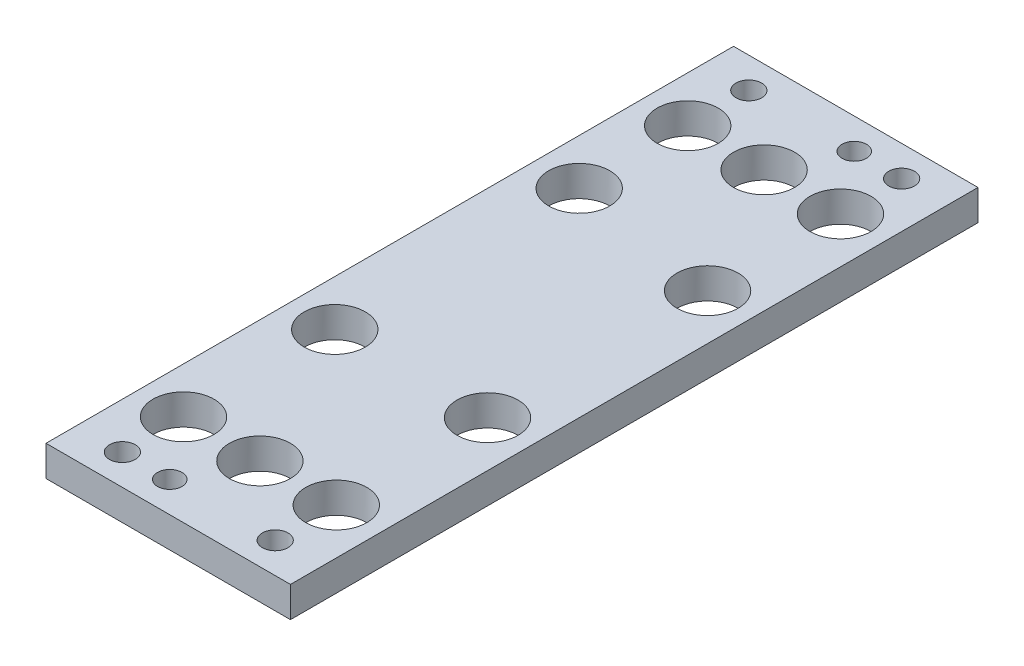
SolidWorks part; units mm, degrees
material "K110"
ref_plane "Front Plane" through (0, 0, 0) normal (0, 0, 1) x (1, 0, 0)
ref_plane "Top Plane" through (0, 0, 0) normal (0, 1, 0) x (1, 0, 0)
ref_plane "Right Plane" through (0, 0, 0) normal (1, 0, 0) x (0, 0, -1)
sketch "Sketch1" plane through (0, 0, 0) normal (0, 1, 0) x (1, 0, 0)
  line L1 (-40, -112.5) -> (40, -112.5)
  line L2 (-40, -112.5) -> (-40, 112.5)
  line L3 (-40, 112.5) -> (40, 112.5)
  line L4 (40, -112.5) -> (40, 112.5)
  line L5 (-40, -112.5) -> (40, 112.5) construction
  line L6 (-40, 112.5) -> (40, -112.5) construction
  point P0 (0, 0)
  dimension "D1" = 225
  dimension "D2" = 80
extrude "Boss-Extrude1" add sketch "Sketch1" against normal blind 10
sketch "Sketch2" plane through (0, 0, 0) normal (0, 1, 0) x (1, 0, 0)
  circle A0 centre (25, -82.5) radius 10 construction
  circle A1 centre (0, -82.5) radius 10 construction
  circle A2 centre (-25, -82.5) radius 10 construction
  circle A3 centre (25, -33) radius 10 construction
  circle A4 centre (-25, -33) radius 10 construction
  circle A6 centre (25, 39) radius 10 construction
  circle A7 centre (-25, 47) radius 10 construction
  circle A8 centre (-25, 82.5) radius 10 construction
  circle A9 centre (0, 82.5) radius 10 construction
  circle A10 centre (25, 82.5) radius 10 construction
  circle A11 centre (25, -82.5) radius 10
  circle A12 centre (0, -82.5) radius 10
  circle A13 centre (-25, -82.5) radius 10
  circle A14 centre (25, -33) radius 10
  circle A15 centre (-25, -33) radius 10
  circle A17 centre (25, 39) radius 10
  circle A18 centre (-25, 47) radius 10
  circle A19 centre (-25, 82.5) radius 10
  circle A20 centre (0, 82.5) radius 10
  circle A21 centre (25, 82.5) radius 10
extrude "Cut-Extrude1" cut sketch "Sketch2" against normal up to next
hole_wizard "M8 Clearance Hole1" positions "Sketch9" profile "Sketch8" hole size "M8" standard "ISO" end condition through all
sketch "Sketch9" plane through (0, 0, 0) normal (0, 1, 0) x (1, 0, 0)
  point P0 (25, -102.5)
  point P3 (-25, -102.5)
  point P6 (25, 102.5)
  point P9 (-25, 102.5)
sketch "Sketch8" plane through (25, 0, 102.5) normal (1, 0, 0) x (0, 0, 1)
  line L0 (0, 0) -> (0, 10)
  line L1 (0, 10) -> (4.2, 10)
  line L2 (4.2, 10) -> (4.2, 0)
  line L5 (4.2, 0) -> (0, 0)
  line L11 (0, -6.35) -> (0, 107.95) construction
  dimension "Thru Hole Dia." = 8.4
  dimension "Thru Hole Depth" = 10
hole_wizard "Ø8.0mm Dowel Hole1" positions "Sketch12" profile "Sketch11" hole size "Ø8.0" standard "ISO" end condition through all
sketch "Sketch12" plane through (0, 0, 0) normal (0, 1, 0) x (1, 0, 0)
  point P0 (-9.5, -102.5)
  point P3 (9.5, 102.5)
sketch "Sketch11" plane through (-9.5, 0, 102.5) normal (1, 0, 0) x (0, 0, 1)
  line L0 (0, 0) -> (0, 10)
  line L1 (0, 10) -> (4, 10)
  line L2 (4, 10) -> (4, 0)
  line L5 (4, 0) -> (0, 0)
  line L11 (0, -6.35) -> (0, 107.95) construction
  dimension "Thru Hole Dia." = 8
  dimension "Thru Hole Depth" = 10
